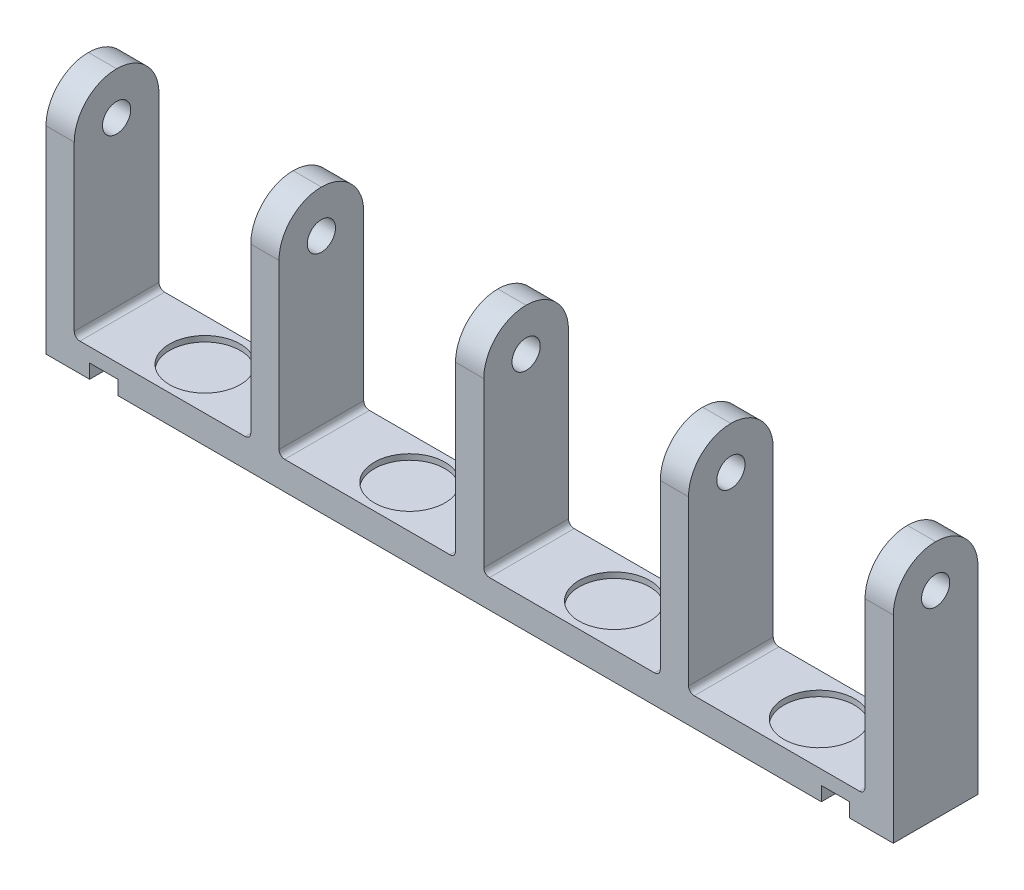
SolidWorks part; units mm, degrees
ref_plane "Front Plane" through (0, 0, 0) normal (0, 0, 1) x (1, 0, 0)
ref_plane "Top Plane" through (0, 0, 0) normal (0, 1, 0) x (1, 0, 0)
ref_plane "Right Plane" through (0, 0, 0) normal (1, 0, 0) x (0, 0, -1)
sketch "Sketch1" plane through (0, 0, 0) normal (0, 1, 0) x (1, 0, 0)
  line L1 (150, 15) -> (-150, 15)
  line L2 (150, 15) -> (150, -15)
  line L3 (150, -15) -> (-150, -15)
  line L4 (-150, 15) -> (-150, -15)
  line L5 (150, 15) -> (-150, -15) construction
  line L6 (150, -15) -> (-150, 15) construction
  point P0 (0, 0)
  dimension "D1" = 300
  dimension "D2" = 30
extrude "Boss-Extrude1" add sketch "Sketch1" along normal mid plane 10
sketch "Sketch2" plane through (0, -5, 0) normal (0, -1, 0) x (1, 0, 0)
  line L0 (-150, 15) -> (150, 15) construction
  line L1 (-134.545, 15) -> (-124.545, 15)
  line L2 (-134.545, 15) -> (-134.545, -15)
  line L3 (-134.545, -15) -> (-124.545, -15)
  line L4 (-124.545, 15) -> (-124.545, -15)
  line L5 (150, -15) -> (-150, -15) construction
  line L7 (134.545, 15) -> (124.545, 15)
  line L8 (134.545, 15) -> (134.545, -15)
  line L9 (134.545, -15) -> (124.545, -15)
  line L10 (124.545, 15) -> (124.545, -15)
  line L11 (0, 0) -> (0, 36.3214) construction
  dimension "D1" = 249.09
  dimension "D2" = 10
  dimension "D3" = 10
extrude "Cut-Extrude1" cut sketch "Sketch2" against normal blind 5
sketch "Sketch3" plane through (0, 0, 0) normal (0, 0, 1) x (1, 0, 0)
  line L0 (-150, 5) -> (-150, 80)
  line L1 (-150, 80) -> (-140, 80)
  line L2 (-140, 80) -> (-140, 5)
  line L3 (-150, 5) -> (150, 5) construction
  line L4 (0, 0) -> (0, 80) construction
  line L5 (140, 80) -> (140, 5)
  line L6 (150, 80) -> (140, 80)
  line L7 (150, 5) -> (150, 80)
  line L8 (-150, 5) -> (-140, 5)
  line L9 (140, 5) -> (150, 5)
  line L10 (-77.5, 5) -> (-77.5, 80)
  line L11 (-77.5, 80) -> (-67.5, 80)
  line L12 (-67.5, 80) -> (-67.5, 5)
  line L13 (-77.5, 5) -> (-67.5, 5)
  line L14 (67.5, 80) -> (67.5, 5)
  line L15 (77.5, 80) -> (67.5, 80)
  line L16 (77.5, 5) -> (77.5, 80)
  line L17 (67.5, 5) -> (77.5, 5)
  line L18 (-5, 5) -> (-5, 80)
  line L19 (-5, 80) -> (5, 80)
  line L20 (5, 80) -> (5, 5)
  line L21 (-5, 5) -> (5, 5)
  dimension "D1" = 10
  dimension "D2" = 75
  dimension "D5" = 62.5
  dimension "D6" = 62.5
  dimension "D8" = 62.5
  dimension "D3" = 2
  dimension "D4" = 2
  dimension "D7" = 2
extrude "Boss-Extrude2" add sketch "Sketch3" along normal mid plane 30
fillet "Fillet1" radius 15 4 edges at (145, 80, -15) (145, 80, 15) (-145, 80, -15) (-145, 80, 15)
sketch "Sketch4" plane through (-150, 0, 0) normal (-1, 0, 0) x (0, 0, 1)
  circle A0 centre (0, 65) radius 5
  arc A1 (15, 65) -> (0, 80) centre (0, 65) ccw construction
  dimension "D1" = 10
extrude "Cut-Extrude2" cut sketch "Sketch4" against normal through all
fillet "Fillet2" radius 15 6 edges at (72.5, 80, -15) (72.5, 80, 15) (0, 80, -15) (0, 80, 15) (-72.5, 80, -15) (-72.5, 80, 15)
fillet "Fillet3" radius 2 8 edges at (-77.5, 5, 0) (-5, 5, 0) (67.5, 5, 0) (140, 5, 0) (77.5, 5, 0) (5, 5, 0) (-67.5, 5, 0) (-140, 5, 0)
sketch "Sketch5" plane through (0, 5, 0) normal (0, 1, 0) x (1, 0, 0)
  line L0 (7, -15) -> (65.5, -15) construction
  line L1 (7, 15) -> (7, -15) construction
  circle A0 centre (36.25, 0) radius 12.5
  point P4 (36.25, -15)
  point P7 (7, 0)
  dimension "D1" = 25
extrude "Cut-Extrude3" cut sketch "Sketch5" against normal blind 2
pattern_linear "LPattern1" count 3 spacing 72.5 along (-1, 0, 0) count 3 spacing 72.5 along (1, 0, 0) of "Cut-Extrude3"
